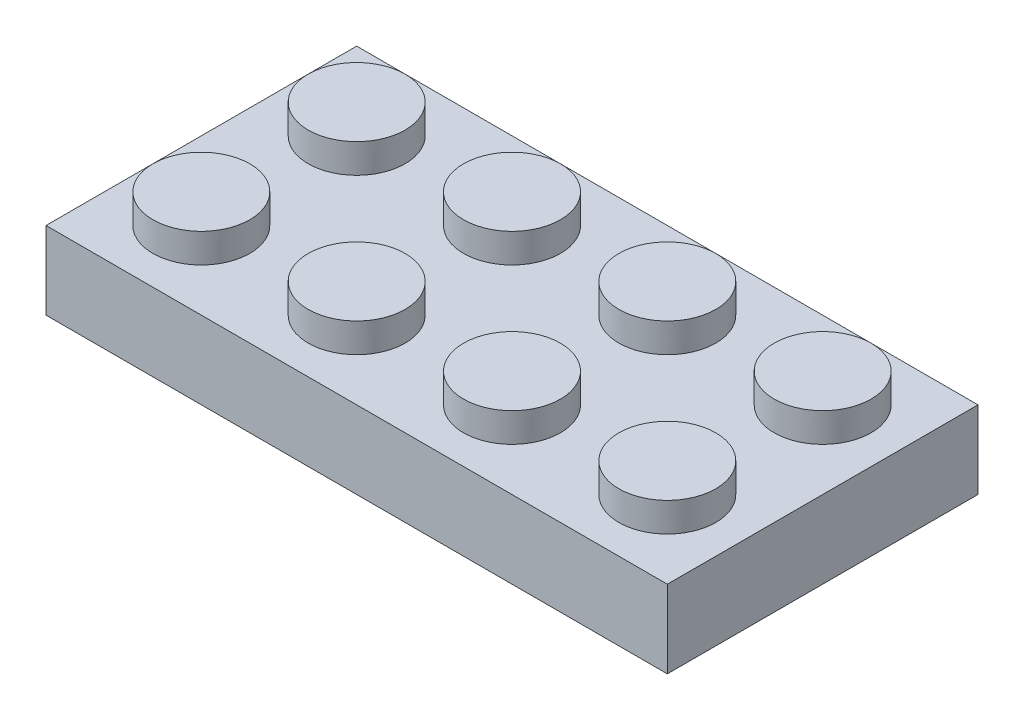
SolidWorks part; units mm, degrees
ref_plane "Front Plane" through (0, 0, 0) normal (0, 0, 1) x (1, 0, 0)
ref_plane "Top Plane" through (0, 0, 0) normal (0, 1, 0) x (1, 0, 0)
ref_plane "Right Plane" through (0, 0, 0) normal (1, 0, 0) x (0, 0, -1)
sketch "Sketch2" plane through (0, 0, 0) normal (0, 1, 0) x (1, 0, 0)
  line L1 (0, 0) -> (25.4, 0)
  line L2 (0, 0) -> (0, 12.7)
  line L3 (0, 12.7) -> (25.4, 12.7)
  line L4 (25.4, 0) -> (25.4, 12.7)
  circle A0 centre (3.175, 9.525) radius 1.9812
  point P9 (0, 9.5676)
  dimension "D5" = 3.9624
  dimension "D1" = 12.7
  dimension "D2" = 25.4
  dimension "D3" = 3.175
  dimension "D4" = 3.175
extrude "Boss-Extrude1" add sketch "Sketch2" against normal blind 3.175 contours L1 L4 L3 L2
extrude "Boss-Extrude2" add sketch "Sketch2<3>" along normal blind 1.1938 contours A0
sketch "Sketch2<3>" plane through (0, 0, 0) normal (0, 1, 0) x (1, 0, 0) same geometry as "Sketch2"
pattern_linear "LPattern1" count 4 spacing 6.35 along (1, 0, 0) count 2 spacing 6.35 along (0, 0, 1) of "Boss-Extrude2"
shell "Shell1" thickness 1.1938 removed face at (12.7, -3.175, -6.35)
sketch "Sketch4" plane through (0, -1.1938, 0) normal (0, -1, 0) x (1, 0, 0)
  line L0 (0, 0) -> (0, -12.7) construction
  line L1 (0, 0) -> (25.4, 0) construction
  circle A0 centre (6.35, -6.3639) radius 2.5019
  circle A1 centre (6.35, -6.3639) radius 1.9812
  dimension "D3" = 5.0038
  dimension "D4" = 3.9624
  dimension "D1" = 6.35
  dimension "D2" = 6.3639
extrude "Boss-Extrude3" add sketch "Sketch4" along normal up to surface (1.9812 mm away) up to face at (12.7, -3.175, -6.35)
fillet "Fillet1" radius 1.1938 1 edges at (1.1938, -2.1844, -1.1938)
fillet "Fillet2" radius 1.1938 3 edges at (24.2062, -2.1844, -1.1938) (24.2062, -2.1844, -11.5062) (1.1938, -2.1844, -11.5062)
pattern_linear "LPattern2" count 3 spacing 6.35 along (1, 0, 0) of "Boss-Extrude3"
